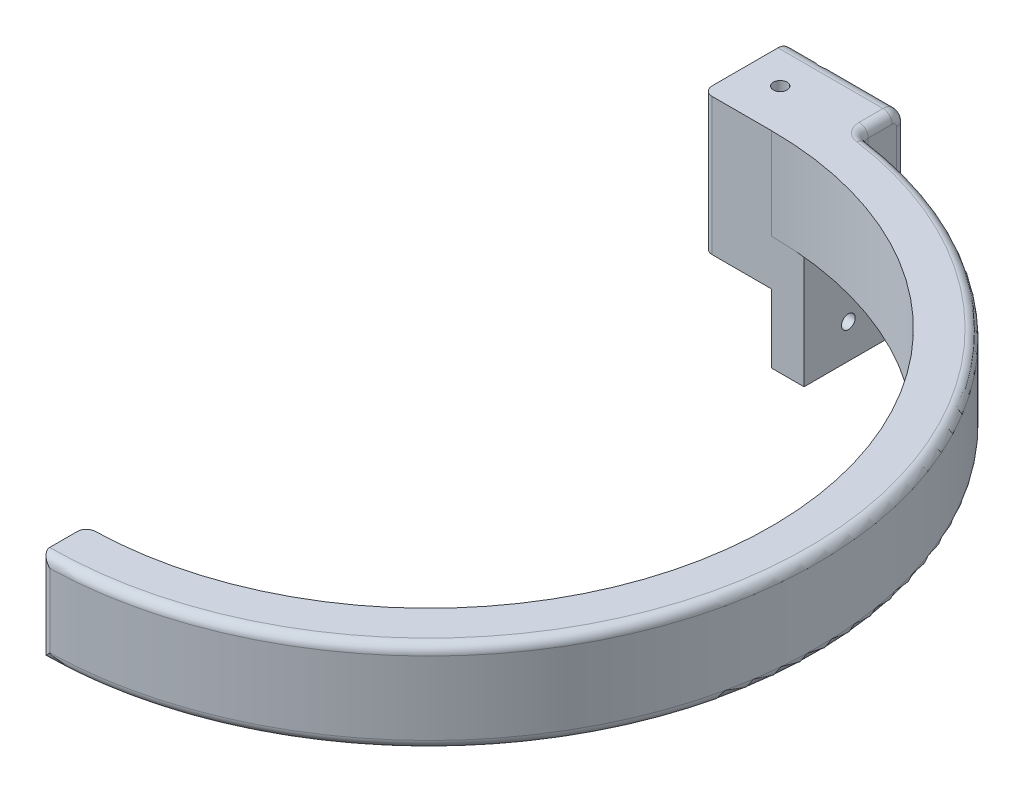
SolidWorks part; units mm, degrees
ref_plane "Front Plane" through (0, 0, 0) normal (0, 0, 1) x (1, 0, 0)
ref_plane "Top Plane" through (0, 0, 0) normal (0, 1, 0) x (1, 0, 0)
ref_plane "Right Plane" through (0, 0, 0) normal (1, 0, 0) x (0, 0, -1)
sketch "Sketch1" plane through (0, 0, 0) normal (0, 1, 0) x (1, 0, 0)
  line L0 (0, -75) -> (0, -85)
  line L1 (0, 75) -> (0, 94.4097)
  line L2 (0, 94.4097) -> (10, 94.4097)
  line L3 (10, 94.4097) -> (10, 84.4097)
  line L4 (10, 89.4097) -> (5, 89.4097) construction
  arc A0 (0, -75) -> (0, 75) centre (0, 0) ccw
  arc A1 (0, -85) -> (10, 84.4097) centre (0, 0) ccw
  dimension "D4" = 10
  dimension "D1" = 75
  dimension "D2" = 10
  dimension "D3" = 10
  dimension "D7" = 5
extrude "Boss-Extrude1" add sketch "Sketch1" along normal blind 20
sketch "Sketch3" plane through (0, 0, 0) normal (-1, 0, 0) x (0, 0, 1)
  line L5 (-75, 20) -> (-75, 0) construction
  line L6 (-94.4097, 20) -> (-75, 20)
  line L7 (-94.4097, 20) -> (-94.4097, -10)
  line L8 (-94.4097, -10) -> (-75, -10)
  line L9 (-75, 20) -> (-75, -10)
  dimension "D1" = 30
extrude "Boss-Extrude3" add sketch "Sketch3" along normal blind 15
fillet "Fillet1" radius 2 10 edges at (10, 0, -89.4097) (10, 20, -89.4097) (84.8523, 0, 5.0087) (84.8523, 20, 5.0087) (0, 10, 85) (0, 10, 75) (-15, 5, -75) (-15, 5, -94.4097) (10, 10, -94.4097) (10, 10, -84.4097)
ref_plane "Plane1" through (-20, 0, 0) normal (1, 0, 0) x (0, 0, -1)
sketch "Sketch4" plane through (0, 20, 0) normal (0, 1, 0) x (1, 0, 0)
  line L0 (8, 94.4097) -> (-13, 94.4097) construction
  line L2 (0, 94.4097) -> (0, 75) construction
  circle A0 centre (-7.5, 84.4097) radius 1.5
  circle A1 centre (-7.5, 94.4097) radius 1.5
  dimension "D1" = 3
  dimension "D2" = 10
  dimension "D3" = 10
  dimension "D4" = 7.5
extrude "Cut-Extrude1" cut sketch "Sketch4" against normal through all
fillet "Fillet2" radius 3 3 edges at (9.4142, 19.4142, -93.8239) (-11, 20, -94.4097) (1, 20, -94.4097)
sketch "Sketch5" plane through (0, 0, 0) normal (0, -1, 0) x (-1, 0, 0)
  line L0 (-4, 94.4097) -> (-4, 89.4722) construction
  line L1 (-8, 94.4097) -> (0, 94.4097) construction
  line L2 (0, 94.4097) -> (0, 75) construction
  line L3 (-8, 101.2119) -> (0, 101.2119)
  line L4 (-8, 101.2119) -> (-8, 77.7326)
  line L5 (-8, 77.7326) -> (0, 77.7326)
  line L6 (0, 101.2119) -> (0, 77.7326)
  line L7 (-8, 101.2119) -> (0, 77.7326) construction
  line L8 (-8, 77.7326) -> (0, 101.2119) construction
sketch "Sketch7" plane through (0, 0, 0) normal (0, -1, 0) x (-1, 0, 0)
  line L0 (0, 84.7049) -> (-7.1189, 84.7049) construction
  line L1 (0, 94.4097) -> (0, 75) construction
  line L3 (-7.1189, 94.4097) -> (0, 94.4097)
  line L4 (-7.1189, 94.4097) -> (-7.1189, 75)
  line L5 (-7.1189, 75) -> (0, 75)
  line L6 (0, 94.4097) -> (0, 75)
  line L7 (-7.1189, 94.4097) -> (0, 75) construction
  line L8 (-7.1189, 75) -> (0, 94.4097) construction
  point P4 (-3.5594, 84.7049)
extrude "Boss-Extrude5" add sketch "Sketch7" along normal blind 25
sketch "Sketch8" plane through (7.1189, 0, 0) normal (1, 0, 0) x (0, 0, -1)
  line L0 (84.7049, -25) -> (84.7049, -16.3114) construction
  line L1 (94.4097, -25) -> (75, -25) construction
sketch "Sketch9" plane through (7.1189, 0, 0) normal (1, 0, 0) x (0, 0, -1)
  line L0 (84.7049, -25) -> (84.7049, -17.5) construction
  line L1 (94.4097, -25) -> (75, -25) construction
  circle A0 centre (84.7049, -17.5) radius 1.5
  dimension "D1" = 3
extrude "Cut-Extrude3" cut sketch "Sketch9" against normal up to next
